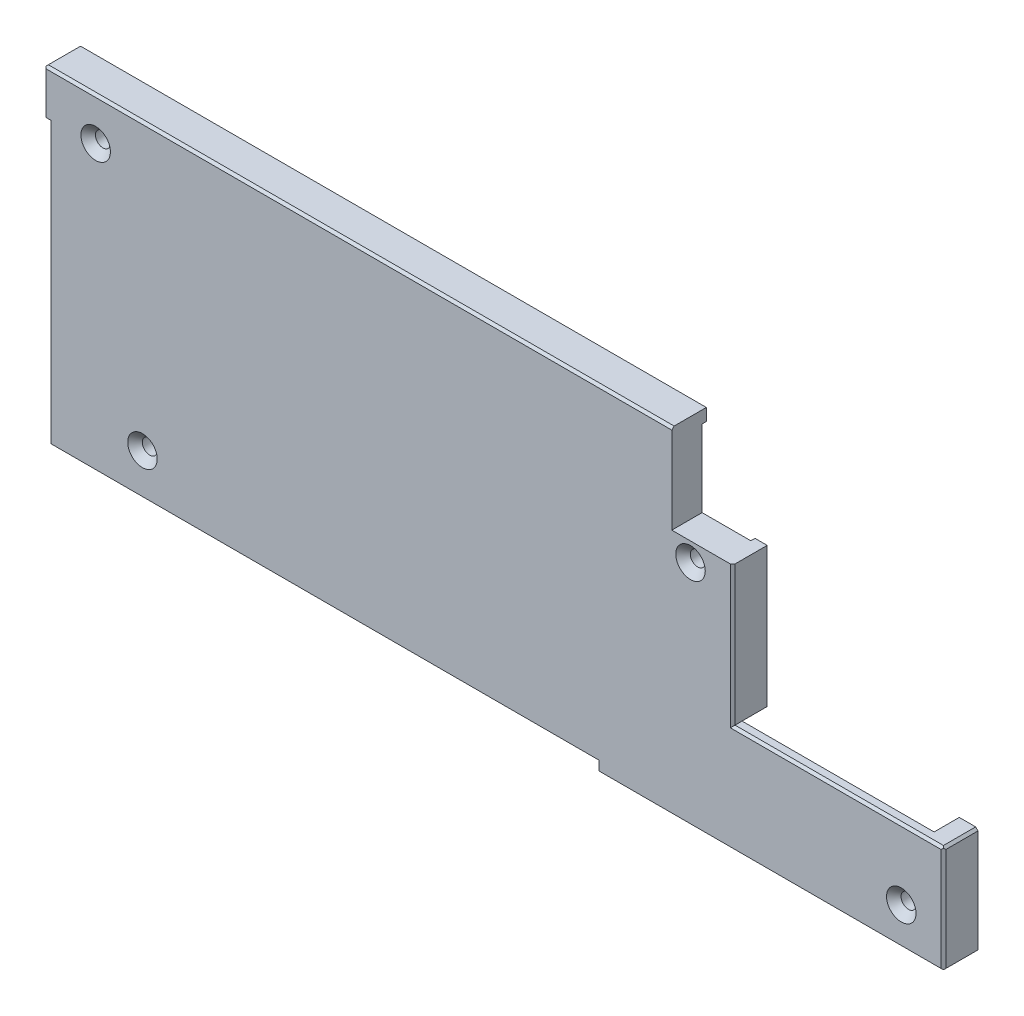
SolidWorks part; units mm, degrees
ref_plane "Front Plane" through (0, 0, 0) normal (0, 0, 1) x (1, 0, 0)
ref_plane "Top Plane" through (0, 0, 0) normal (0, 1, 0) x (1, 0, 0)
ref_plane "Right Plane" through (0, 0, 0) normal (1, 0, 0) x (0, 0, -1)
sketch "Sketch1" plane through (0, 0, 0) normal (0, 0, 1) x (1, 0, 0)
  line L11 (-95.4641, -40.9644) -> (21.5359, -40.9644)
  line L12 (21.5359, -40.9644) -> (21.5359, -42.9644)
  line L13 (21.5359, -42.9644) -> (95.5359, -42.9644)
  line L14 (95.5359, -42.9644) -> (95.5359, -19.9644)
  line L15 (95.5359, -19.9644) -> (50.5359, -19.9644)
  line L16 (50.5359, -19.9644) -> (50.5359, 28.8356)
  line L17 (50.5359, 28.8356) -> (-95.4641, 28.8356)
  line L18 (-95.4641, 18.8356) -> (-95.4641, -40.9644)
  line L20 (22.5359, -37.9644) -> (-95.0641, -37.9644) construction
  line L21 (-91.0641, 25.8356) -> (47.1359, 25.8356) construction
  line L22 (47.5359, 25.4356) -> (47.5359, -19.9644) construction
  line L23 (92.5359, -23.3644) -> (92.5359, -40.5644) construction
  line L24 (92.1359, -40.9644) -> (24.9359, -40.9644) construction
  line L25 (24.5359, -40.5644) -> (24.5359, -39.9644) construction
  line L26 (77.1859, -22.9644) -> (92.1359, -22.9644) construction
  line L27 (-95.4641, -37.5644) -> (-95.4641, -32.9934) construction
  line L28 (-95.4641, 18.8356) -> (-96.5641, 18.8356)
  line L29 (-96.5641, 18.8356) -> (-96.5641, 28.8356)
  line L30 (-96.5641, 28.8356) -> (-95.4641, 28.8356)
  dimension "D1" = 3
  dimension "D2" = 3
  dimension "D3" = 69.8
  dimension "D4" = 3
  dimension "D5" = 3
  dimension "D6" = 2
  dimension "D7" = 3
  dimension "D8" = 3
  dimension "D9" = 1.1
  dimension "D10" = 10
extrude "Boss-Extrude1" add sketch "Sketch1" along normal blind 7.375
sketch "Sketch2" plane through (0, 0, 0) normal (0, 0, -1) x (-1, 0, 0)
  line L75 (95.4641, 14.9066) -> (95.4641, -36.9644)
  line L77 (-91.5359, -23.9644) -> (-91.5359, -19.9644)
  line L78 (-95.5359, -19.9644) -> (-50.5359, -19.9644) construction
  line L79 (-91.5359, -19.9644) -> (-46.5359, -19.9644)
  line L95 (-77.7859, -27.9644) -> (-77.7859, -23.9644)
  line L96 (-77.7859, -23.9644) -> (-91.5359, -23.9644)
  line L97 (-91.5359, -23.9644) -> (-91.5359, -39.9644)
  line L98 (-91.5359, -39.9644) -> (-25.5359, -39.9644)
  line L99 (-22.5359, -36.9644) -> (94.4641, -36.9644)
  line L100 (94.4641, -36.9644) -> (94.4641, -33.5934)
  line L101 (94.4641, -33.5934) -> (88.5641, -33.5934)
  line L102 (87.1641, -32.1934) -> (87.1641, -28.2434)
  line L103 (88.1641, -26.9018) -> (88.1641, 5.2149)
  line L104 (87.1641, 6.5566) -> (87.1641, 10.5066)
  line L105 (88.5641, 11.9066) -> (94.4641, 11.9066)
  line L106 (94.4641, 11.9066) -> (94.4641, 14.9066)
  line L107 (94.4641, 14.9066) -> (91.8641, 14.9066)
  line L108 (90.4641, 16.3066) -> (90.4641, 24.8356)
  line L109 (90.4641, 24.8356) -> (-46.5359, 24.8356)
  line L110 (-46.5359, 24.8356) -> (-46.5359, -19.9644)
  line L111 (-50.5359, -23.9644) -> (-74.2859, -23.9644)
  line L112 (-74.2859, -23.9644) -> (-74.2859, -27.9644)
  line L115 (-91.5359, -23.9644) -> (-91.5359, -39.9644)
  line L116 (-91.5359, -39.9644) -> (-25.5359, -39.9644)
  line L117 (-22.5359, -36.9644) -> (95.4641, -36.9644)
  line L125 (95.4641, 14.9066) -> (91.8641, 14.9066)
  line L126 (90.4641, 16.3066) -> (90.4641, 24.8356)
  line L127 (90.4641, 24.8356) -> (-46.5359, 24.8356)
  line L128 (-46.5359, 24.8356) -> (-46.5359, -19.9644)
  arc A81 (-22.5359, -36.9644) -> (-25.5359, -39.9644) centre (-22.5359, -39.9644) ccw
  arc A82 (87.1641, -32.1934) -> (88.5641, -33.5934) centre (88.5641, -32.1934) ccw
  arc A83 (88.1641, -26.9018) -> (87.1641, -28.2434) centre (88.5641, -28.2434) ccw
  arc A84 (87.1641, 6.5566) -> (88.1641, 5.2149) centre (88.5641, 6.5566) ccw
  arc A85 (88.5641, 11.9066) -> (87.1641, 10.5066) centre (88.5641, 10.5066) ccw
  arc A86 (90.4641, 16.3066) -> (91.8641, 14.9066) centre (91.8641, 16.3066) ccw
  arc A87 (-50.5359, -23.9644) -> (-46.5359, -19.9644) centre (-50.5359, -19.9644) ccw
  arc A88 (-77.7859, -27.9644) -> (-74.2859, -27.9644) centre (-76.0359, -27.9644) ccw
  arc A89 (-22.5359, -36.9644) -> (-25.5359, -39.9644) centre (-22.5359, -39.9644) ccw
  arc A94 (90.4641, 16.3066) -> (91.8641, 14.9066) centre (91.8641, 16.3066) ccw
  dimension "D1" = 1
extrude "Cut-Extrude1" cut sketch "Sketch2" against normal offset from surface (5.375 mm away) 2 up to face at (-4.8841, -11.2444, 7.375)
sketch "Sketch3" plane through (0, 0, 0) normal (0, 0, -1) x (-1, 0, 0)
  line L42 (-76.3859, -27.9644) -> (-76.3859, -23.3644)
  line L43 (-77.1859, -22.5644) -> (-92.1359, -22.5644)
  line L44 (-92.9359, -23.3644) -> (-92.9359, -40.5644)
  line L45 (-92.1359, -41.3644) -> (-24.9359, -41.3644)
  line L46 (-24.1359, -40.5644) -> (-24.1359, -39.9644)
  line L47 (-22.5359, -38.3644) -> (95.0641, -38.3644)
  line L48 (95.8641, -37.5644) -> (95.8641, -32.9934)
  line L49 (95.0641, -32.1934) -> (88.5641, -32.1934)
  line L50 (88.5641, -32.1934) -> (88.5641, -28.2434)
  line L51 (88.5641, -28.2434) -> (88.7641, -28.2434)
  line L52 (89.5641, -27.4434) -> (89.5641, 5.7566)
  line L53 (88.7641, 6.5566) -> (88.5641, 6.5566)
  line L54 (88.5641, 6.5566) -> (88.5641, 10.5066)
  line L55 (88.5641, 10.5066) -> (95.0641, 10.5066)
  line L56 (95.8641, 11.3066) -> (95.8641, 15.5066)
  line L57 (95.0641, 16.3066) -> (91.8641, 16.3066)
  line L58 (91.8641, 16.3066) -> (91.8641, 25.4356)
  line L59 (91.0641, 26.2356) -> (-47.1359, 26.2356)
  line L60 (-47.9359, 25.4356) -> (-47.9359, -19.9644)
  line L61 (-50.5359, -22.5644) -> (-74.8859, -22.5644)
  line L62 (-75.6859, -23.3644) -> (-75.6859, -27.9644)
  line L65 (-92.9359, -23.3644) -> (-92.9359, -40.5644)
  line L66 (-92.1359, -41.3644) -> (-24.9359, -41.3644)
  line L67 (-24.1359, -40.5644) -> (-24.1359, -39.9644)
  line L68 (-22.5359, -38.3644) -> (95.0641, -38.3644)
  line L77 (95.8641, -37.5644) -> (95.8641, 15.5066)
  line L78 (95.0641, 16.3066) -> (91.8641, 16.3066)
  line L79 (91.8641, 16.3066) -> (91.8641, 25.4356)
  line L80 (91.0641, 26.2356) -> (-47.1359, 26.2356)
  line L81 (-47.9359, 25.4356) -> (-47.9359, -19.9644)
  line L82 (-50.5359, -22.5644) -> (-92.1359, -22.5644)
  arc A42 (-76.3859, -23.3644) -> (-77.1859, -22.5644) centre (-77.1859, -23.3644) ccw
  arc A43 (-92.1359, -22.5644) -> (-92.9359, -23.3644) centre (-92.1359, -23.3644) ccw
  arc A44 (-92.9359, -40.5644) -> (-92.1359, -41.3644) centre (-92.1359, -40.5644) ccw
  arc A45 (-24.9359, -41.3644) -> (-24.1359, -40.5644) centre (-24.9359, -40.5644) ccw
  arc A46 (-22.5359, -38.3644) -> (-24.1359, -39.9644) centre (-22.5359, -39.9644) ccw
  arc A47 (95.0641, -38.3644) -> (95.8641, -37.5644) centre (95.0641, -37.5644) ccw
  arc A48 (95.8641, -32.9934) -> (95.0641, -32.1934) centre (95.0641, -32.9934) ccw
  arc A49 (88.7641, -28.2434) -> (89.5641, -27.4434) centre (88.7641, -27.4434) ccw
  arc A50 (89.5641, 5.7566) -> (88.7641, 6.5566) centre (88.7641, 5.7566) ccw
  arc A51 (95.0641, 10.5066) -> (95.8641, 11.3066) centre (95.0641, 11.3066) ccw
  arc A52 (95.8641, 15.5066) -> (95.0641, 16.3066) centre (95.0641, 15.5066) ccw
  arc A53 (91.8641, 25.4356) -> (91.0641, 26.2356) centre (91.0641, 25.4356) ccw
  arc A54 (-47.1359, 26.2356) -> (-47.9359, 25.4356) centre (-47.1359, 25.4356) ccw
  arc A55 (-50.5359, -22.5644) -> (-47.9359, -19.9644) centre (-50.5359, -19.9644) ccw
  arc A56 (-74.8859, -22.5644) -> (-75.6859, -23.3644) centre (-74.8859, -23.3644) ccw
  arc A57 (-76.3859, -27.9644) -> (-75.6859, -27.9644) centre (-76.0359, -27.9644) ccw
  arc A59 (-92.1359, -22.5644) -> (-92.9359, -23.3644) centre (-92.1359, -23.3644) ccw
  arc A60 (-92.9359, -40.5644) -> (-92.1359, -41.3644) centre (-92.1359, -40.5644) ccw
  arc A61 (-24.9359, -41.3644) -> (-24.1359, -40.5644) centre (-24.9359, -40.5644) ccw
  arc A62 (-22.5359, -38.3644) -> (-24.1359, -39.9644) centre (-22.5359, -39.9644) ccw
  arc A63 (95.0641, -38.3644) -> (95.8641, -37.5644) centre (95.0641, -37.5644) ccw
  arc A68 (95.8641, 15.5066) -> (95.0641, 16.3066) centre (95.0641, 15.5066) ccw
  arc A69 (91.8641, 25.4356) -> (91.0641, 26.2356) centre (91.0641, 25.4356) ccw
  arc A70 (-47.1359, 26.2356) -> (-47.9359, 25.4356) centre (-47.1359, 25.4356) ccw
  arc A71 (-50.5359, -22.5644) -> (-47.9359, -19.9644) centre (-50.5359, -19.9644) ccw
  dimension "D1" = 0.4
extrude "Cut-Extrude2" cut sketch "Sketch3" against normal blind 0.9
sketch "Sketch5" plane through (0, 0, 5.375) normal (0, 0, -1) x (-1, 0, 0)
  line L0 (-46.5359, 24.8356) -> (90.4641, 24.8356) construction
  line L1 (-39.5359, 1.8356) -> (-46.5359, 1.8356)
  line L3 (-35.5359, 24.8356) -> (-46.5359, 24.8356)
  line L4 (-46.5359, 1.8356) -> (-46.5359, 24.8356)
  line L5 (81.4641, 24.8356) -> (93.6641, 24.8356)
  line L6 (81.4641, 24.8356) -> (81.4641, 18.9066)
  line L7 (85.4641, 14.9066) -> (93.6641, 14.9066)
  line L8 (93.6641, 24.8356) -> (93.6641, 14.9066)
  line L9 (91.8641, 14.9066) -> (95.4641, 14.9066) construction
  line L10 (95.4641, -36.9644) -> (-22.5359, -36.9644) construction
  line L11 (71.4641, -36.9644) -> (79.4641, -36.9644)
  line L12 (71.4641, -36.9644) -> (71.4641, -31.9644)
  line L14 (79.4641, -36.9644) -> (79.4641, -31.9644)
  line L15 (-91.5359, -39.9644) -> (-91.5359, -22.5644) construction
  line L16 (-91.5359, -30.9644) -> (-86.5359, -30.9644)
  line L17 (-91.5359, -30.9644) -> (-91.5359, -39.9644)
  line L18 (-91.5359, -39.9644) -> (-82.5359, -39.9644)
  line L19 (-82.5359, -34.9644) -> (-82.5359, -39.9644)
  line L20 (-25.5359, -39.9644) -> (-91.5359, -39.9644) construction
  line L28 (-35.5359, 5.8356) -> (-35.5359, 24.8356)
  line L29 (-46.5359, 24.8356) -> (90.4641, 24.8356) construction
  circle A0 centre (-41.5359, 19.8356) radius 2
  circle A1 centre (-41.5359, 5.8356) radius 2
  circle A2 centre (-86.5359, -34.9644) radius 2
  circle A3 centre (85.4641, 19.8356) radius 2
  circle A4 centre (75.4641, -31.9644) radius 2
  arc A6 (79.4641, -31.9644) -> (71.4641, -31.9644) centre (75.4641, -31.9644) ccw
  arc A9 (-82.5359, -34.9644) -> (-86.5359, -30.9644) centre (-86.5359, -34.9644) ccw
  arc A10 (-39.5359, 1.8356) -> (-35.5359, 5.8356) centre (-39.5359, 5.8356) ccw
  circle A11 centre (-86.5359, -34.9644) radius 4 construction
  circle A12 centre (75.4641, -31.9644) radius 4 construction
  arc A13 (81.4641, 18.9066) -> (85.4641, 14.9066) centre (85.4641, 18.9066) ccw
  dimension "D1" = 4
  dimension "D4" = 4
  dimension "D3" = 4
  dimension "D5" = 4
  dimension "D6" = 6
  dimension "D2" = 2
extrude "Boss-Extrude2" add sketch "Sketch5" along normal up to surface (4.475 mm away) up to face at (-42.6582, 14.8632, 0.9)
chamfer "Chamfer1" distance 0.5 angle 45 10 edges at (95.5359, -31.4644, 7.375) (58.5359, -42.9644, 7.375) (21.5359, -41.9644, 7.375) (-36.9641, -40.9644, 7.375) (-95.4641, -11.0644, 7.375) (-96.0141, 18.8356, 7.375) (-96.5641, 23.8356, 7.375) (-23.0141, 28.8356, 7.375) (50.5359, 4.4356, 7.375) (73.0359, -19.9644, 7.375)
chamfer "Chamfer2" distance 0.5 angle 45 7 edges at (-96.5641, 18.8356, 3.4375) (-96.5641, 28.8356, 3.4375) (-95.4641, -40.9644, 3.4375) (21.5359, -42.9644, 3.4375) (95.5359, -42.9644, 3.4375) (95.5359, -19.9644, 3.4375) (50.5359, 28.8356, 3.4375)
sketch "Sketch9" plane through (0, 0, 0) normal (0, 0, -1) x (-1, 0, 0)
  line L1 (-50.5359, 28.8356) -> (-37.5359, 28.8356)
  line L2 (-50.5359, 28.8356) -> (-50.5359, 9.8356)
  line L3 (-50.5359, 9.8356) -> (-37.5359, 9.8356)
  line L4 (-37.5359, 28.8356) -> (-37.5359, 9.8356)
  line L5 (-50.5359, -19.9644) -> (-50.5359, 28.3356) construction
  line L6 (-50.0359, 28.8356) -> (96.0641, 28.8356) construction
  circle A0 centre (-41.5359, 5.8356) radius 2 construction
  dimension "D1" = 4
  dimension "D2" = 4
extrude "Cut-Extrude3" cut sketch "Sketch9" against normal through all
sketch "Sketch10" plane through (0, 0, 0.9) normal (0, 0, -1) x (-1, 0, 0)
  circle A14 centre (-41.5359, 5.8356) radius 2.1
  circle A15 centre (85.4641, 19.8356) radius 2.1
  circle A16 centre (75.4641, -31.9644) radius 2.1
  circle A17 centre (-86.5359, -34.9644) radius 2.1
  circle A18 centre (-41.5359, 5.8356) radius 2 construction
  dimension "D1" = 0.1
extrude "Boss-Extrude3" add sketch "Sketch10" against normal through all
hole_wizard "CSK for M3 Flat Head Machine Screw2" positions "Sketch11" profile "Sketch12" countersink size "M3" standard "ANSI Metric" end condition through all
sketch "Sketch11" plane through (0, 0, 7.375) normal (0, 0, 1) x (1, 0, 0)
  point P0 (-85.4641, 19.8356)
  point P3 (41.5359, 5.8356)
  point P6 (86.5359, -34.9644)
  point P9 (-75.4641, -31.9644)
  point P20 (-85.4641, 18.9066)
  point P21 (-81.1185, 19.5879)
  point P22 (-85.4641, 19.8356)
  dimension "D1" = 2
sketch "Sketch12" plane through (-85.4641, 19.8356, 7.375) normal (1, 0, 0) x (0, -1, 0)
  line L0 (0, 0) -> (0, 7.375)
  line L1 (0, 7.375) -> (1.6, 7.375)
  line L2 (1.6, 7.375) -> (1.6, 1.55)
  line L3 (1.6, 1.55) -> (3.15, 0)
  line L5 (3.15, 0) -> (0, 0)
  line L6 (-1.6, 1.55) -> (-3.15, 0) construction
  line L11 (0, -6.35) -> (0, 107.95) construction
  dimension "Thru Hole Dia." = 3.2
  dimension "Thru Hole Depth" = 7.375
  dimension "Near C'Sink Dia." = 6.3
  dimension "Near C'Sink Angle" = 90
